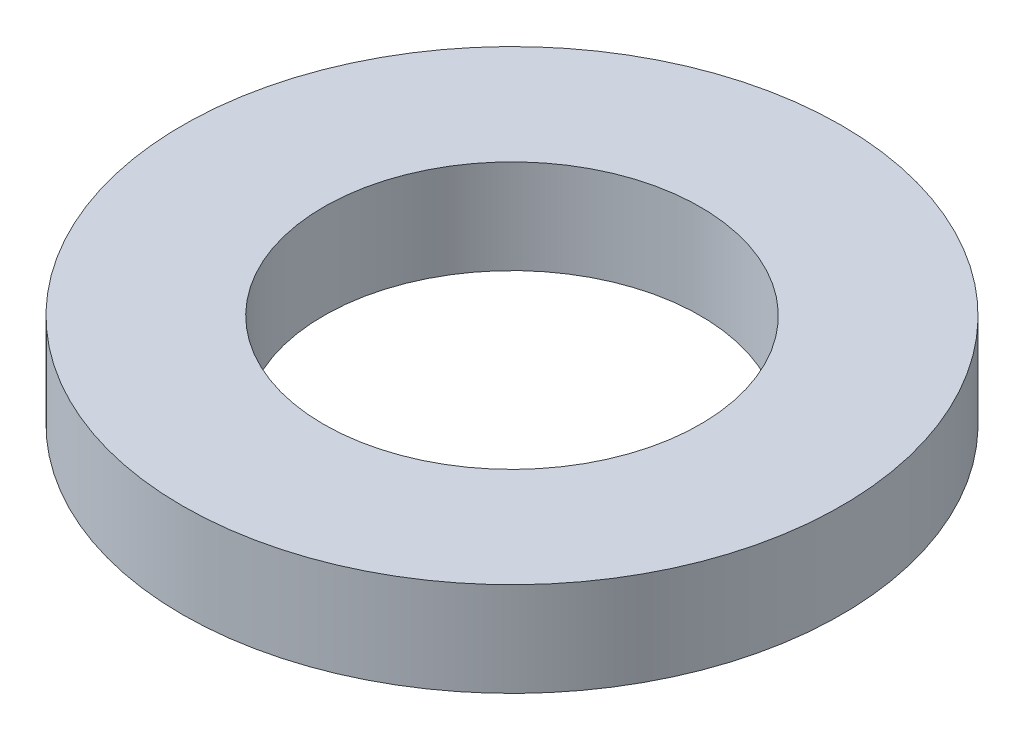
SolidWorks part; units mm, degrees
ref_plane "Front Plane" through (0, 0, 0) normal (0, 0, 1) x (1, 0, 0)
ref_plane "Top Plane" through (0, 0, 0) normal (0, 1, 0) x (1, 0, 0)
ref_plane "Right Plane" through (0, 0, 0) normal (1, 0, 0) x (0, 0, -1)
sketch "Sketch1" plane through (0, 0, 0) normal (0, 1, 0) x (1, 0, 0)
  circle A0 centre (0, 0) radius 52.5
  dimension "FLANGE_OD" = 105
extrude "Boss-Extrude1" add sketch "Sketch1" along normal blind 15
sketch "Sketch2" plane through (0, 0, 0) normal (0, 1, 0) x (1, 0, 0)
  circle A0 centre (0, 0) radius 30
  dimension "BORE_D" = 60
extrude "Cut-Extrude1" cut sketch "Sketch2" along normal through all
sketch "Sketch3" plane through (0, 15, 0) normal (0, 1, 0) x (1, 0, 0)
  circle A0 centre (0, 0) radius 21.9122 construction
  circle A1 centre (-21.9122, 0) radius 2.7824
  dimension "BOLT_D" = 5.5648
  dimension "BOLT_PCD" = 43.8245
extrude "Cut-Extrude2" cut sketch "Sketch3" against normal blind 9.4123 rebuild error yes
pattern_circular "CirPattern1" count 4 over 360 rebuild error yes
